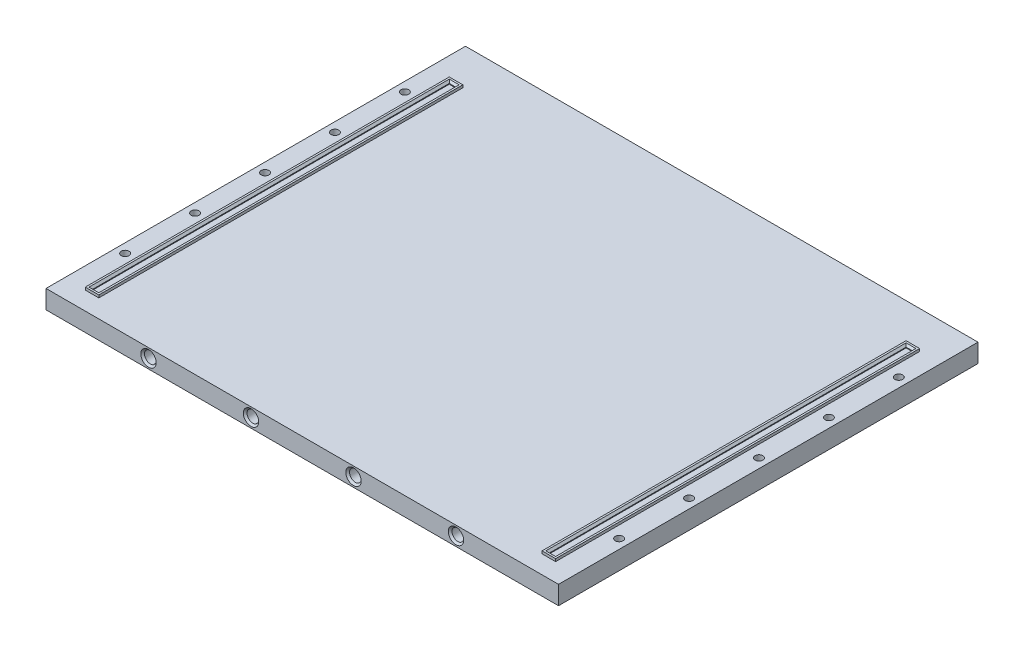
SolidWorks part; units mm, degrees
ref_plane "Спереди" through (0, 0, 0) normal (0, 0, 1) x (1, 0, 0)
ref_plane "Сверху" through (0, 0, 0) normal (0, 1, 0) x (1, 0, 0)
ref_plane "Справа" through (0, 0, 0) normal (1, 0, 0) x (0, 0, -1)
sketch "Эскиз1" plane through (0, 0, 0) normal (0, 1, 0) x (1, 0, 0)
  line L5 (-69.03, -56.5) -> (69.03, -56.5)
  line L6 (-69.03, -56.5) -> (-69.03, 56.5)
  line L7 (-69.03, 56.5) -> (69.03, 56.5)
  line L8 (69.03, -56.5) -> (69.03, 56.5)
  line L9 (-69.03, -56.5) -> (69.03, 56.5) construction
  line L10 (-69.03, 56.5) -> (69.03, -56.5) construction
  point P0 (0, 0)
  dimension "D1" = 113
  dimension "D2" = 138.06
extrude "Основание" add sketch "Эскиз1" along normal blind 5
sketch "Эскиз6" plane through (0, 0, 0) normal (0, -1, 0) x (1, 0, 0)
  line L0 (0, 45.5668) -> (0, -26.923) construction
  line L1 (-15.8226, 0) -> (3.0664, 0) construction
  line L2 (-37, 37) -> (0, 37) construction
  line L3 (-47, 47) -> (-27, 47)
  line L4 (-47, 47) -> (-47, 27)
  line L5 (-47, 27) -> (-27, 27)
  line L6 (-27, 47) -> (-27, 27)
  line L7 (-47, 47) -> (-27, 27) construction
  line L8 (-47, 27) -> (-27, 47) construction
  line L9 (-37, 37) -> (-37, 0) construction
  line L10 (47, 47) -> (27, 47)
  line L11 (47, 47) -> (47, 27)
  line L12 (47, 27) -> (27, 27)
  line L13 (27, 47) -> (27, 27)
  line L14 (27, -47) -> (27, -27)
  line L15 (47, -27) -> (27, -27)
  line L16 (47, -47) -> (47, -27)
  line L17 (47, -47) -> (27, -47)
  line L18 (-47, -47) -> (-27, -47)
  line L19 (-47, -47) -> (-47, -27)
  line L20 (-47, -27) -> (-27, -27)
  line L21 (-27, -47) -> (-27, -27)
  point P1 (-37, 37)
  dimension "D1" = 20
  dimension "D2" = 37
sketch "Эскиз2" plane through (0, 5, 0) normal (0, 1, 0) x (1, 0, 0)
  line L0 (0, 0) -> (0, -25.5598) construction
  line L1 (-61.525, 37.0772) -> (-61.525, 5.6487) construction
  line L2 (-21.6597, -2.575) -> (12.5108, -2.575) construction
  line L3 (-59.7, 46.45) -> (-63.35, 46.45)
  line L4 (-63.35, 46.45) -> (-63.35, -51.6)
  line L5 (-63.35, -2.575) -> (-62.35, -2.575)
  line L6 (-62.35, -50.6) -> (-62.35, 45.45)
  line L7 (-62.35, 45.45) -> (-60.7, 45.45)
  line L8 (-61.525, 45.45) -> (-61.525, 46.45)
  line L9 (-60.7, -50.6) -> (-60.7, 45.45)
  line L10 (-59.7, -2.575) -> (-60.7, -2.575)
  line L11 (-59.7, 46.45) -> (-59.7, -51.6)
  line L12 (-62.35, -50.6) -> (-60.7, -50.6)
  line L13 (-59.7, -51.6) -> (-63.35, -51.6)
  line L14 (-61.525, -50.6) -> (-61.525, -51.6)
  line L15 (61.525, -50.6) -> (61.525, -51.6)
  line L16 (59.7, -51.6) -> (63.35, -51.6)
  line L17 (62.35, -50.6) -> (60.7, -50.6)
  line L18 (59.7, 46.45) -> (59.7, -51.6)
  line L19 (59.7, -2.575) -> (60.7, -2.575)
  line L20 (60.7, -50.6) -> (60.7, 45.45)
  line L21 (61.525, 45.45) -> (61.525, 46.45)
  line L22 (62.35, 45.45) -> (60.7, 45.45)
  line L23 (62.35, -50.6) -> (62.35, 45.45)
  line L24 (63.35, -2.575) -> (62.35, -2.575)
  line L25 (63.35, 46.45) -> (63.35, -51.6)
  line L26 (59.7, 46.45) -> (63.35, 46.45)
  line L27 (-69.03, -56.5) -> (69.03, -56.5) construction
  dimension "D1" = 1
  dimension "D2" = 96.05
  dimension "D3" = 1.65
  dimension "D4" = 121.4
  dimension "D5" = 5.9
extrude "Ложемент материнской платы" add sketch "Эскиз2" along normal blind 0.7 contours L14 L12 L6 L5 L4 L13 | L7 L8 L3 L4 L5 L6 | L11 L3 L8 L7 L9 L10 | L12 L14 L13 L11 L10 L9 | L26 L21 L22 L23 L24 L25 | L26 L18 L19 L20 L22 L21 | L17 L20 L19 L18 L16 L15 | L25 L24 L23 L17 L15 L16 region at (-60.2151, 5, -22.3349) region at (-62.8349, 5, -22.3349) region at (-60.2151, 5, 27.4849) region at (-62.8349, 5, 27.4849) region at (62.8349, 5, 27.4849) region at (60.2151, 5, 27.4849) region at (62.8349, 5, -22.3349) region at (60.2151, 5, -22.3349)
fillet "Фаска первого ложемента" radius 0.5 4 edges at (-61.525, 5.7, -45.45) (-60.7, 5.7, 2.575) (-61.525, 5.7, 50.6) (-62.35, 5.7, 2.575) type face fillet profile chamfer first side face at (-61.525, 5.35, -45.45) first side face at (-61.525, 5.35, 50.6) first side face at (-60.7, 5.35, 2.575) first side face at (-62.35, 5.35, 2.575) second side face at (-61.525, 5.7, 2.575)
fillet "Фаска второго ложемента" radius 0.5 4 edges at (61.525, 5.7, 50.6) (60.7, 5.7, 2.575) (61.525, 5.7, -45.45) (62.35, 5.7, 2.575) type face fillet profile chamfer first side face at (61.525, 5.35, -45.45) first side face at (62.35, 5.35, 2.575) first side face at (60.7, 5.35, 2.575) first side face at (61.525, 5.35, 50.6) second side face at (61.525, 5.7, 2.575)
sketch "Эскиз3" plane through (0, 0, -56.5) normal (0, 0, -1) x (-1, 0, 0)
  line L0 (-69.03, 0) -> (69.03, 0) construction
  line L1 (-69.03, 5) -> (-69.03, 0) construction
  line L2 (-41.418, 2.5) -> (-69.03, 2.5) construction
  line L3 (41.418, 2.5) -> (69.03, 2.5) construction
  line L6 (69.03, 5) -> (69.03, 0) construction
  line L7 (-41.418, 2.5) -> (-13.806, 2.5) construction
  line L8 (-13.806, 2.5) -> (13.806, 2.5) construction
  line L9 (13.806, 2.5) -> (41.418, 2.5) construction
  circle A0 centre (-41.418, 2.5) radius 1.575
  circle A1 centre (-13.806, 2.5) radius 1.575
  circle A2 centre (13.806, 2.5) radius 1.575
  circle A3 centre (41.418, 2.5) radius 1.575
  dimension "D4" = 3.15
  dimension "D1" = 2.5
  dimension "D5" = 27.612
  dimension "D3" = 4
extrude "Крепежные отверсия передней и задней стенки" cut sketch "Эскиз3" against normal blind 4.2
ref_plane "Плоскость1" through (0, 0, 0) normal (0, 0, -1) x (-1, 0, 0)
mirror "Зеркальное отражение1" about plane through (0, 0, 0) normal (0, 0, -1) of "Крепежные отверсия передней и задней стенки"
sketch "Эскиз4" plane through (0, 0, 0) normal (0, -1, 0) x (1, 0, 0)
  line L0 (0, 34.8353) -> (0, -23.754) construction
  line L1 (-66.53, 56.5) -> (-66.53, 37.6667) construction
  line L2 (-69.03, 56.5) -> (69.03, 56.5) construction
  line L3 (-66.53, 37.6667) -> (-66.53, 18.8333) construction
  line L4 (-66.53, 18.8333) -> (-66.53, 0) construction
  line L5 (-66.53, 0) -> (-66.53, -18.8333) construction
  line L6 (-66.53, -18.8333) -> (-66.53, -37.6667) construction
  line L7 (-66.53, -37.6667) -> (-66.53, -56.5) construction
  line L8 (69.03, -56.5) -> (-69.03, -56.5) construction
  line L9 (-69.03, -56.5) -> (-69.03, 56.5) construction
  circle A0 centre (-66.53, 37.6667) radius 1.05
  circle A1 centre (-66.53, 18.8333) radius 1.05
  circle A2 centre (-66.53, 0) radius 1.05
  circle A3 centre (-66.53, -18.8333) radius 1.05
  circle A4 centre (-66.53, -37.6667) radius 1.05
  circle A5 centre (66.53, -37.6667) radius 1.05
  circle A6 centre (66.53, -18.8333) radius 1.05
  circle A7 centre (66.53, 0) radius 1.05
  circle A8 centre (66.53, 18.8333) radius 1.05
  circle A9 centre (66.53, 37.6667) radius 1.05
  dimension "D3" = 2.1
  dimension "D2" = 2.5
  dimension "D1" = 5
extrude "Отверстия крепежных винтов" cut sketch "Эскиз4" against normal up to next
sketch "Эскиз5" plane through (0, 0, 0) normal (0, -1, 0) x (1, 0, 0)
  line L0 (0, 88.0608) -> (0, 29.4715) construction
  line L1 (-66.53, 56.5) -> (-66.53, 37.6667) construction
  line L2 (-66.53, 37.6667) -> (-66.53, 18.8333) construction
  line L3 (-66.53, 18.8333) -> (-66.53, 0) construction
  line L4 (-66.53, 0) -> (-66.53, -18.8333) construction
  line L5 (-66.53, -18.8333) -> (-66.53, -37.6667) construction
  line L6 (-66.53, -37.6667) -> (-66.53, -56.5) construction
  line L7 (69.03, -56.5) -> (-69.03, -56.5) construction
  line L8 (-69.03, 56.5) -> (69.03, 56.5) construction
  circle A0 centre (-66.53, 37.6667) radius 2
  circle A1 centre (-66.53, 18.8333) radius 2
  circle A2 centre (-66.53, 0) radius 2
  circle A3 centre (-66.53, -18.8333) radius 2
  circle A4 centre (-66.53, -37.6667) radius 2
  circle A5 centre (66.53, -37.6667) radius 2
  circle A6 centre (66.53, -18.8333) radius 2
  circle A7 centre (66.53, 0) radius 2
  circle A8 centre (66.53, 18.8333) radius 2
  circle A9 centre (66.53, 37.6667) radius 2
  circle A10 centre (-66.53, -37.6667) radius 1.05 construction
  dimension "D1" = 4
extrude "Потай головок винтов" cut sketch "Эскиз5" against normal blind 3
chamfer "Фаска под запресовку" distance 0.5 angle 45 8 edges at (39.843, 2.5, 56.5) (12.231, 2.5, 56.5) (-15.381, 2.5, 56.5) (-42.993, 2.5, 56.5) (-42.993, 2.5, -56.5) (-15.381, 2.5, -56.5) (12.231, 2.5, -56.5) (39.843, 2.5, -56.5)
